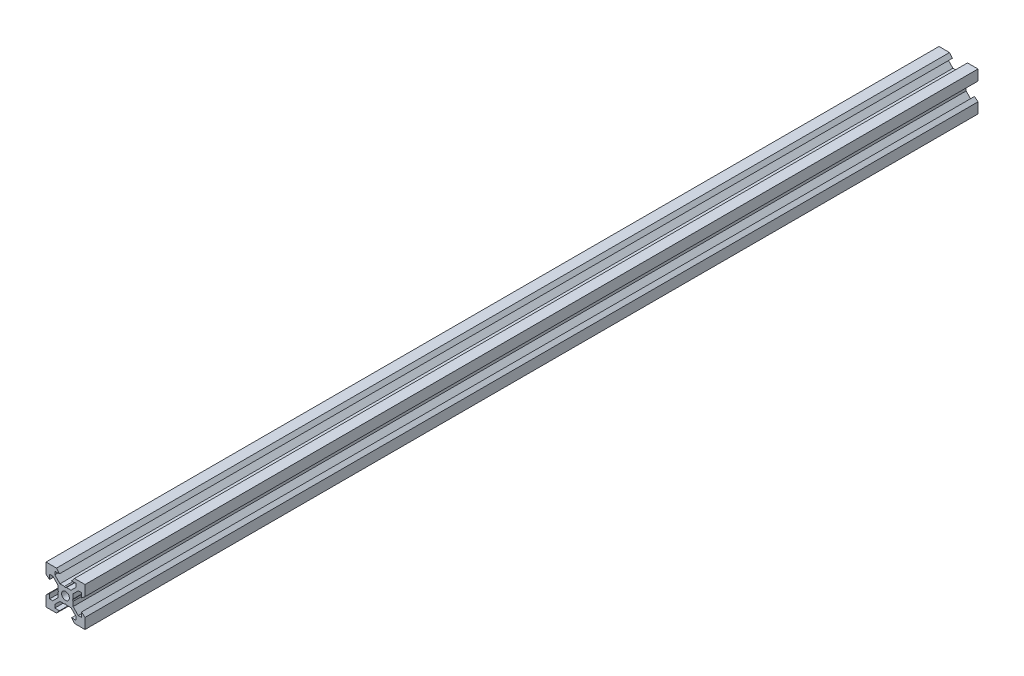
SolidWorks part; units mm, degrees
ref_plane "Front Plane" through (0, 0, 0) normal (0, 0, 1) x (1, 0, 0)
ref_plane "Top Plane" through (0, 0, 0) normal (0, 1, 0) x (1, 0, 0)
ref_plane "Right Plane" through (0, 0, 0) normal (1, 0, 0) x (0, 0, -1)
sketch "Sketch1" plane through (0, 0, 0) normal (0, 0, 1) x (1, 0, 0)
  line L0 (10, 10) -> (4.6104, 10) construction
  line L1 (10, 10) -> (10, 4.6104) construction
  line L2 (10, -10) -> (10, -4.6104) construction
  line L3 (10, -10) -> (4.6104, -10) construction
  line L4 (10, 10) -> (10, 4.6104)
  line L5 (6.5607, 5.5) -> (8.2, 5.5)
  line L6 (5.5, 8.2) -> (5.5, 6.5607)
  line L7 (10, 10) -> (4.6104, 10)
  line L8 (10, 10) -> (10, 4.6104)
  line L9 (6.5607, 5.5) -> (3.9, 2.8393)
  line L10 (5.5, 6.5607) -> (2.8393, 3.9)
  line L11 (10, 4.6104) -> (8.2, 3.1)
  line L12 (4.6104, 10) -> (3.1, 8.2)
  line L13 (8.2, 3.1) -> (8.2, 5.5)
  line L14 (3.1, 8.2) -> (5.5, 8.2)
  line L15 (-6.5607, 5.5) -> (-8.2, 5.5)
  line L16 (6.5607, -5.5) -> (8.2, -5.5)
  line L17 (3.1, -8.2) -> (5.5, -8.2)
  line L18 (8.2, -3.1) -> (8.2, -5.5)
  line L19 (4.6104, -10) -> (3.1, -8.2)
  line L20 (10, -4.6104) -> (8.2, -3.1)
  line L21 (0.5196, -3.9) -> (0, -3.6)
  line L22 (0.5196, 3.9) -> (0, 3.6)
  line L23 (3.6, 0) -> (3.9, -0.5196)
  line L24 (3.9, 0.5196) -> (3.6, 0)
  line L25 (3.9, 0.5196) -> (3.9, 2.8393)
  line L26 (2.8393, 3.9) -> (0.5196, 3.9)
  line L27 (3.9, -2.8393) -> (3.9, -0.5196)
  line L28 (2.8393, -3.9) -> (0.5196, -3.9)
  line L29 (5.5, -6.5607) -> (2.8393, -3.9)
  line L30 (6.5607, -5.5) -> (3.9, -2.8393)
  line L31 (10, -10) -> (10, -4.6104)
  line L32 (10, -10) -> (4.6104, -10)
  line L33 (5.5, -8.2) -> (5.5, -6.5607)
  line L34 (-6.5607, -5.5) -> (-8.2, -5.5)
  line L35 (10, -10) -> (10, -4.6104)
  line L36 (0, 0) -> (0, 8.2) construction
  line L37 (-10, -10) -> (-4.6104, -10) construction
  line L38 (-10, -10) -> (-10, -4.6104) construction
  line L39 (-10, 10) -> (-10, 4.6104) construction
  line L40 (-10, 10) -> (-4.6104, 10) construction
  line L41 (-10, -10) -> (-10, -4.6104)
  line L43 (-5.5, -8.2) -> (-5.5, -6.5607)
  line L44 (-10, -10) -> (-4.6104, -10)
  line L45 (-10, -10) -> (-10, -4.6104)
  line L46 (-6.5607, -5.5) -> (-3.9, -2.8393)
  line L47 (-5.5, -6.5607) -> (-2.8393, -3.9)
  line L48 (-2.8393, -3.9) -> (-0.5196, -3.9)
  line L49 (-3.9, -2.8393) -> (-3.9, -0.5196)
  line L50 (-2.8393, 3.9) -> (-0.5196, 3.9)
  line L51 (-3.9, 0.5196) -> (-3.9, 2.8393)
  line L52 (-3.9, 0.5196) -> (-3.6, 0)
  line L53 (-3.6, 0) -> (-3.9, -0.5196)
  line L54 (-0.5196, 3.9) -> (0, 3.6)
  line L55 (-0.5196, -3.9) -> (0, -3.6)
  line L56 (-10, -4.6104) -> (-8.2, -3.1)
  line L57 (-4.6104, -10) -> (-3.1, -8.2)
  line L58 (-8.2, -3.1) -> (-8.2, -5.5)
  line L59 (-3.1, -8.2) -> (-5.5, -8.2)
  line L60 (-10, -10) -> (10, -10) construction
  line L61 (-10, -10) -> (-10, 10) construction
  line L62 (-3.1, 8.2) -> (-5.5, 8.2)
  line L63 (-8.2, 3.1) -> (-8.2, 5.5)
  line L64 (-4.6104, 10) -> (-3.1, 8.2)
  line L65 (-10, 4.6104) -> (-8.2, 3.1)
  line L66 (-5.5, 6.5607) -> (-2.8393, 3.9)
  line L67 (-6.5607, 5.5) -> (-3.9, 2.8393)
  line L68 (-10, 10) -> (-10, 4.6104)
  line L69 (-10, 10) -> (-4.6104, 10)
  line L70 (-5.5, 8.2) -> (-5.5, 6.5607)
  line L71 (-10, 10) -> (10, 10) construction
  line L72 (-10, 10) -> (-10, 4.6104)
  line L73 (10, -10) -> (10, 10) construction
  line L74 (-10, -10) -> (10, 10) construction
  line L75 (-10, 10) -> (10, -10) construction
  circle A0 centre (0, 0) radius 2
  dimension "D7" = 4
  dimension "D1" = 20
  dimension "D2" = 5.3896
  dimension "D3" = 4.5
  dimension "D4" = 50
  dimension "D5" = 1.8
  dimension "D6" = 1.5104
  dimension "D8" = 5.5
  dimension "D9" = 120
  dimension "D10" = 0.3
  dimension "D11" = 2.3197
  dimension "D12" = 7.8
  dimension "D13" = 7.8
  dimension "D14" = 1.5
  dimension "D15" = 2.6607
extrude "Boss-Extrude1" add sketch "Sketch1" along normal mid plane 458 contours L70 L62 L64 L69 L68 L65 L63 L15 L67 L51 L52 L53 L49 L46 L34 L58 L56 L41 L44 L57 L59 L43 L47 L48 L55 L21 L28 L29 L33 L17 L19 L32 L31 L20 L18 L16 L30 L27 L23 L24 L25 L9 L5 L13 L11 L4 L7 L12 L14 L6 L10 region at (9.7172, 7.3052, 0)
